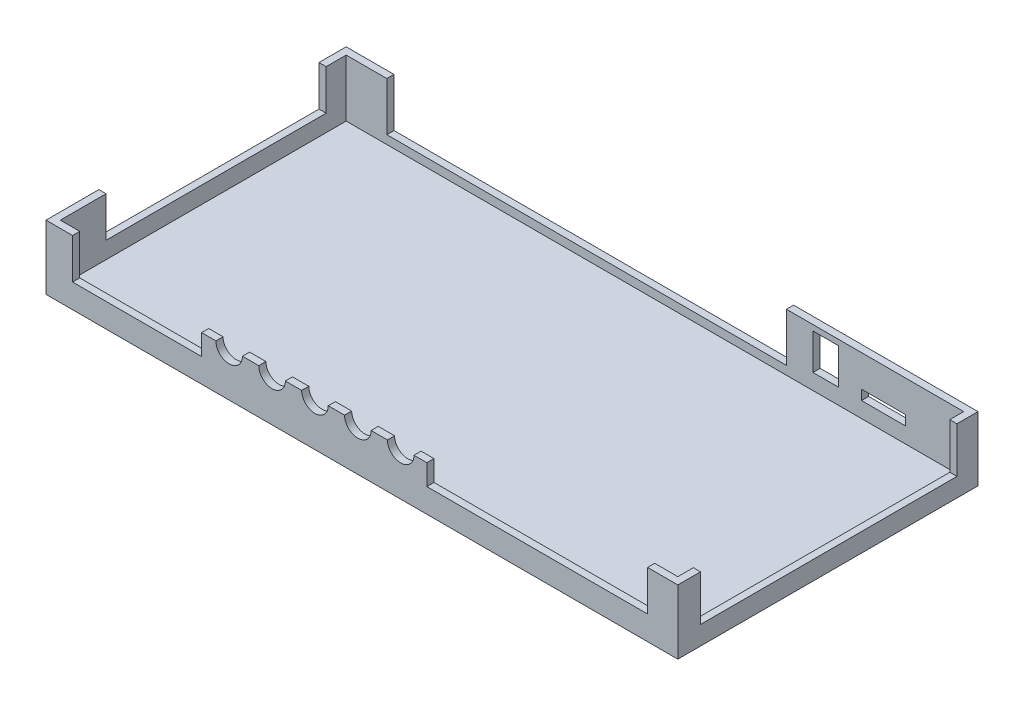
SolidWorks part; units mm, degrees
ref_plane "Front Plane" through (0, 0, 0) normal (0, 0, 1) x (1, 0, 0)
ref_plane "Top Plane" through (0, 0, 0) normal (0, 1, 0) x (1, 0, 0)
ref_plane "Right Plane" through (0, 0, 0) normal (1, 0, 0) x (0, 0, -1)
sketch "Sketch1" plane through (0, 0, 0) normal (0, 1, 0) x (1, 0, 0)
  line L0 (-110.5, -52.5) -> (-110.5, 52.5)
  line L1 (-108, -50) -> (108, -50)
  line L2 (-108, -50) -> (-108, 50)
  line L3 (-108, 50) -> (108, 50)
  line L4 (108, -50) -> (108, 50)
  line L5 (-108, -50) -> (108, 50) construction
  line L6 (-108, 50) -> (108, -50) construction
  line L7 (-110.5, 52.5) -> (110.5, 52.5)
  line L8 (110.5, -52.5) -> (110.5, 52.5)
  line L9 (-110.5, -52.5) -> (110.5, -52.5)
  point P0 (0, 0)
  dimension "D1" = 216
  dimension "D2" = 100
  dimension "D3" = 2.5
extrude "Boss-Extrude1" add sketch "Sketch1" along normal blind 20 contours L0 L9 L8 L7 L4 L1 L2 L3 region at (-108.0532, 0, 0)
extrude "Boss-Extrude2" add sketch "Sketch1<3>" against normal blind 2.5 contours L0 L7 L8 L9
sketch "Sketch1<3>" plane through (0, 0, 0) normal (0, 1, 0) x (1, 0, 0) same geometry as "Sketch1"
ref_plane "Plane1" through (-110.5, 20, 52.5) normal (1, 0, 0) x (0, 0, -1)
sketch "Sketch3" plane through (0, 0, 52.5) normal (0, 0, 1) x (1, 0, 0)
  line L0 (-110.5, 20) -> (110.5, 20) construction
  line L1 (-101.2008, 20) -> (99.9204, 20)
  line L2 (-101.2008, 20) -> (-101.2008, 5.8947)
  line L3 (-101.2008, 5.8947) -> (99.9204, 5.8947)
  line L4 (99.9204, 20) -> (99.9204, 5.8947)
extrude "Cut-Extrude1" cut sketch "Sketch3" against normal blind 10
sketch "Sketch4" plane through (110.5, 0, 0) normal (1, 0, 0) x (0, 0, -1)
  line L0 (-52.5, 20) -> (52.5, 20) construction
  line L1 (-44.5761, 20) -> (45.1289, 20)
  line L2 (-44.5761, 20) -> (-44.5761, 4.0461)
  line L3 (-44.5761, 4.0461) -> (45.1289, 4.0461)
  line L4 (45.1289, 20) -> (45.1289, 4.0461)
  point P6 (41.3027, 4.0937)
  point P7 (-41.1929, 4.0461)
extrude "Cut-Extrude2" cut sketch "Sketch4" against normal blind 10
sketch "Sketch5" plane through (0, 0, 52.5) normal (0, 0, 1) x (1, 0, 0)
  line L0 (-144.165, 13.1347) -> (142.8743, 13.1347) construction
  line L1 (-101.2008, 5.8947) -> (99.9204, 5.8947) construction
  line L2 (0, -12.375) -> (0, 12.375) construction
  line L4 (-56.08, 5.8947) -> (22.72, 5.8947)
  line L6 (-41.78, 13.1347) -> (-36.08, 13.1347)
  line L7 (-26.78, 13.1347) -> (-21.08, 13.1347)
  line L8 (-11.78, 13.1347) -> (-6.08, 13.1347)
  line L9 (3.22, 13.1347) -> (8.92, 13.1347)
  line L10 (-56.08, 13.1347) -> (-56.08, 5.8947)
  line L11 (-56.08, 13.1347) -> (-51.08, 13.1347)
  line L12 (22.72, 13.1347) -> (22.72, 5.8947)
  line L13 (18.22, 13.1347) -> (22.72, 13.1347)
  circle A0 centre (-46.43, 13.1347) radius 4.65 construction
  circle A1 centre (-31.43, 13.1347) radius 4.65 construction
  circle A2 centre (-16.43, 13.1347) radius 4.65 construction
  circle A3 centre (-1.43, 13.1347) radius 4.65 construction
  circle A4 centre (13.57, 13.1347) radius 4.65 construction
  arc A5 (-51.08, 13.1347) -> (-41.78, 13.1347) centre (-46.43, 13.1347) ccw
  arc A6 (-36.08, 13.1347) -> (-26.78, 13.1347) centre (-31.43, 13.1347) ccw
  arc A7 (-21.08, 13.1347) -> (-11.78, 13.1347) centre (-16.43, 13.1347) ccw
  arc A8 (-6.08, 13.1347) -> (3.22, 13.1347) centre (-1.43, 13.1347) ccw
  arc A9 (8.92, 13.1347) -> (18.22, 13.1347) centre (13.57, 13.1347) ccw
  point P4 (-46.43, 13.1347)
  point P5 (-31.43, 13.1347)
  point P6 (-16.43, 13.1347)
  point P7 (-1.43, 13.1347)
  point P8 (13.57, 13.1347)
  dimension "D7" = 9.3
  dimension "D8" = 5
  dimension "D9" = 4.5
  dimension "D1" = 7.24
  dimension "D2" = 46.43
  dimension "D3" = 31.43
  dimension "D4" = 16.43
  dimension "D5" = 1.43
  dimension "D6" = 13.57
extrude "Boss-Extrude3" add sketch "Sketch5" against normal up to surface (2.5 mm away) up to face at (-0.3201, 11.4737, 50)
sketch "Sketch6" plane through (0, 0, -52.5) normal (0, 0, -1) x (-1, 0, 0)
  line L0 (110.5, 20) -> (-110.5, 20) construction
  line L1 (-46, 20) -> (46, 20)
  line L2 (-46, 20) -> (-46, 3)
  line L3 (-46, 3) -> (46, 3)
  line L4 (46, 20) -> (46, 3)
  line L5 (0, 12.375) -> (0, -12.375) construction
  dimension "D1" = 92
  dimension "D2" = 46
  dimension "D3" = 17
extrude "Cut-Extrude3" cut sketch "Sketch6" against normal blind 10
sketch "Sketch7" plane through (-110.5, 0, 0) normal (-1, 0, 0) x (0, 0, 1)
  line L0 (52.5, 20) -> (-52.5, 20) construction
  line L1 (34, 20) -> (-43, 20)
  line L2 (34, 20) -> (34, 5.9)
  line L3 (34, 5.9) -> (-43, 5.9)
  line L4 (-43, 20) -> (-43, 5.9)
  line L5 (52.5, 20) -> (52.5, -2.5) construction
  line L6 (52.5, -2.5) -> (-52.5, -2.5) construction
  dimension "D1" = 18.5
  dimension "D2" = 7
  dimension "D3" = 8.4
extrude "Cut-Extrude4" cut sketch "Sketch7" against normal blind 10
sketch "Sketch8" plane through (0, 0, -52.5) normal (0, 0, -1) x (-1, 0, 0)
  line L0 (110.5, 20) -> (46, 20) construction
  line L1 (45.2316, 20) -> (93.7751, 20)
  line L2 (45.2316, 20) -> (45.2316, 3)
  line L3 (45.2316, 3) -> (93.7751, 3)
  line L4 (93.7751, 20) -> (93.7751, 3)
  line L5 (-46, 3) -> (46, 3) construction
  point P6 (93.7751, 3.2363)
extrude "Cut-Extrude5" cut sketch "Sketch8" against normal blind 4
sketch "Sketch9" plane through (0, 0, -50) normal (0, 0, 1) x (1, 0, 0)
  line L1 (72.2471, 8.9082) -> (87.6268, 8.9082)
  line L2 (72.2471, 8.9082) -> (72.2471, 5.4667)
  line L3 (72.2471, 5.4667) -> (87.6268, 5.4667)
  line L4 (87.6268, 8.9082) -> (87.6268, 5.4667)
extrude "Cut-Extrude6" cut sketch "Sketch9" against normal blind 4
sketch "Sketch10" plane through (0, 0, -50) normal (0, 0, 1) x (1, 0, 0)
  line L1 (55.2825, 18.0604) -> (64.1512, 18.0604)
  line L2 (55.2825, 18.0604) -> (55.2825, 5.4968)
  line L3 (55.2825, 5.4968) -> (64.1512, 5.4968)
  line L4 (64.1512, 18.0604) -> (64.1512, 5.4968)
extrude "Cut-Extrude7" cut sketch "Sketch10" against normal blind 4
equation "\"D2@Sketch6\"=\"D1@Sketch6\"/2"
